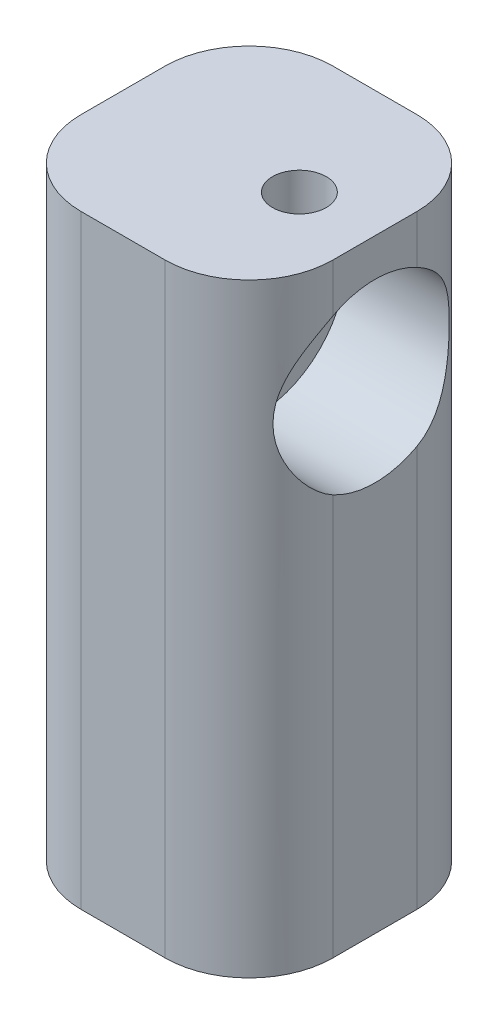
SolidWorks part; units mm, degrees
ref_plane "Front Plane" through (0, 0, 0) normal (0, 0, 1) x (1, 0, 0)
ref_plane "Top Plane" through (0, 0, 0) normal (0, 1, 0) x (1, 0, 0)
ref_plane "Right Plane" through (0, 0, 0) normal (1, 0, 0) x (0, 0, -1)
sketch "Sketch1" plane through (0, 0, 0) normal (0, 1, 0) x (1, 0, 0)
  line L1 (7.5, -7.5) -> (-7.5, -7.5)
  line L2 (7.5, -7.5) -> (7.5, 7.5)
  line L3 (7.5, 7.5) -> (-7.5, 7.5)
  line L4 (-7.5, -7.5) -> (-7.5, 7.5)
  line L5 (7.5, -7.5) -> (-7.5, 7.5) construction
  line L6 (7.5, 7.5) -> (-7.5, -7.5) construction
  circle A0 centre (0, 0) radius 4.25
  point P0 (0, 0)
  dimension "D1" = 8.5
  dimension "D2" = 15
extrude "Boss-Extrude1" add sketch "Sketch1" along normal blind 20
sketch "Sketch2" plane through (0, 20, 0) normal (0, 1, 0) x (1, 0, 0)
  line L1 (-7.5, -7.5) -> (7.5, -7.5)
  line L2 (-7.5, -7.5) -> (-7.5, 7.5)
  line L3 (-7.5, 7.5) -> (7.5, 7.5)
  line L4 (7.5, -7.5) -> (7.5, 7.5)
  line L5 (-7.5, -7.5) -> (7.5, 7.5) construction
  line L6 (-7.5, 7.5) -> (7.5, -7.5) construction
  point P0 (0, 0)
extrude "Boss-Extrude2" add sketch "Sketch2" along normal blind 16
sketch "Sketch3" plane through (7.5, 0, 0) normal (1, 0, 0) x (0, 0, -1)
  line L0 (-7.5, 36) -> (7.5, 36) construction
  circle A0 centre (0, 28.5) radius 2.5
  dimension "D2" = 5
  dimension "D1" = 7.5
extrude "Cut-Extrude1" cut sketch "Sketch3" against normal through all
fillet "Fillet1" radius 5 4 edges at (-7.5, 18, -7.5) (7.5, 18, -7.5) (-7.5, 18, 7.5) (7.5, 18, 7.5)
sketch "Sketch4" plane through (7.5, 0, 0) normal (1, 0, 0) x (0, 0, -1)
  circle A0 centre (0, 28.5) radius 5.25
  dimension "D1" = 10.5
extrude "Cut-Extrude2" cut sketch "Sketch4" against normal blind 7
sketch "Sketch5" plane through (0, 36, 0) normal (0, 1, 0) x (1, 0, 0)
  circle A0 centre (3, 0) radius 1.6
  dimension "D2" = 3.2
  dimension "D1" = 3
extrude "Cut-Extrude3" cut sketch "Sketch5" against normal up to next
chamfer "Chamfer1" distance 10 angle 1 1 edges at (0, 20, 4.25) first distance on face at (0, 20, 4.25)
